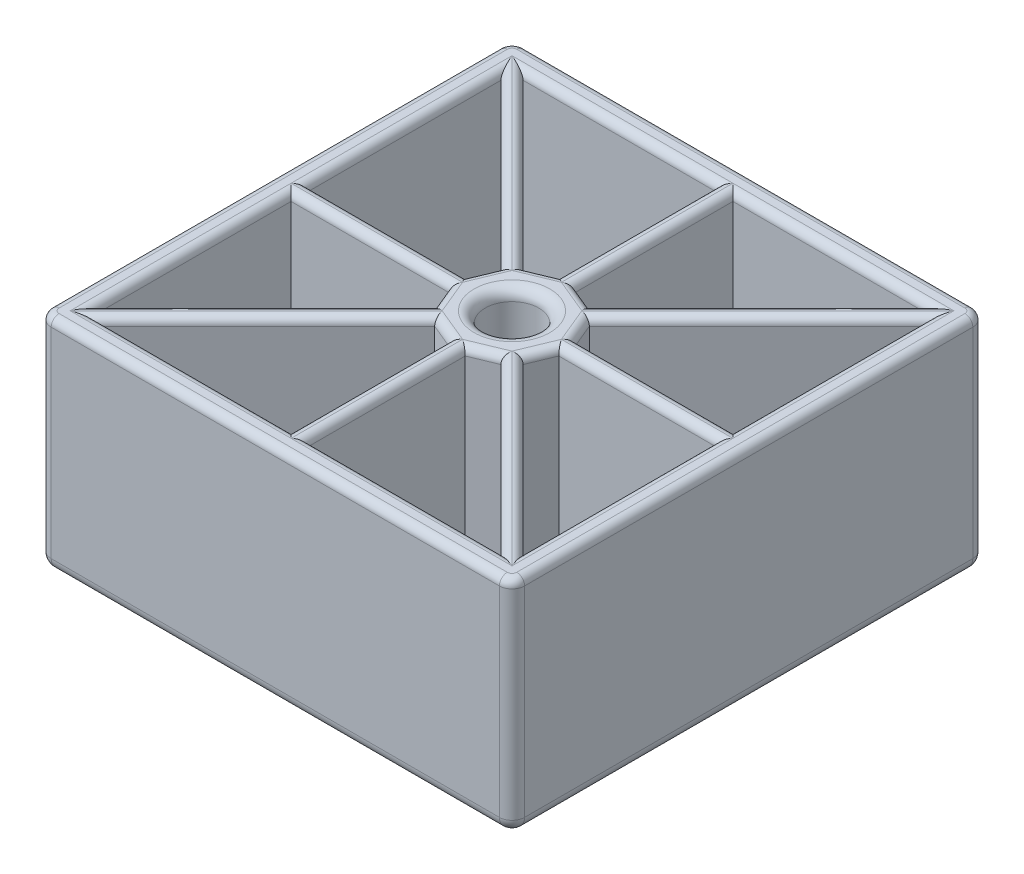
SolidWorks part; units mm, degrees
ref_plane "Front Plane" through (0, 0, 0) normal (0, 0, 1) x (1, 0, 0)
ref_plane "Top Plane" through (0, 0, 0) normal (0, 1, 0) x (1, 0, 0)
ref_plane "Right Plane" through (0, 0, 0) normal (1, 0, 0) x (0, 0, -1)
sketch "Sketch1" plane through (0, 0, 0) normal (0, 1, 0) x (1, 0, 0)
  line L1 (15, -15) -> (-15, -15)
  line L2 (15, -15) -> (15, 15)
  line L3 (15, 15) -> (-15, 15)
  line L4 (-15, -15) -> (-15, 15)
  line L5 (15, -15) -> (-15, 15) construction
  line L6 (15, 15) -> (-15, -15) construction
  point P0 (0, 0)
  dimension "D1" = 30
extrude "Boss-Extrude1" add sketch "Sketch1" along normal blind 14 contours L2 L1 L4 L3
sketch "Sketch2" plane through (0, 14, 0) normal (0, 1, 0) x (1, 0, 0)
  circle A0 centre (0, 0) radius 1.7
extrude "Cut-Extrude1" cut sketch "Sketch2" against normal blind 12
sketch "Sketch3" plane through (0, 14, 0) normal (0, 1, 0) x (1, 0, 0)
  line L0 (-15, 15) -> (15, -15) construction
  line L1 (15, 15) -> (-15, -15) construction
  line L2 (-13.5, -0.5) -> (13.5, -0.5) construction
  line L3 (13.5, -13.5) -> (-13.5, -13.5) construction
  line L4 (13.5, -13.5) -> (13.5, 13.5) construction
  line L5 (13.5, 13.5) -> (-13.5, 13.5) construction
  line L6 (-13.5, -13.5) -> (-13.5, 13.5) construction
  line L7 (13.5, -13.5) -> (-13.5, 13.5) construction
  line L8 (13.5, 13.5) -> (-13.5, -13.5) construction
  line L9 (-13.5, -0.5) -> (-13.5, 0.5) construction
  line L10 (0.5, -13.5) -> (-0.5, -13.5) construction
  line L11 (0.5, -13.5) -> (0.5, 13.5) construction
  line L12 (0.5, 13.5) -> (-0.5, 13.5) construction
  line L13 (-0.5, -13.5) -> (-0.5, 13.5) construction
  line L14 (0.5, -13.5) -> (-0.5, 13.5) construction
  line L15 (0.5, 13.5) -> (-0.5, -13.5) construction
  line L16 (-13.5, 0.5) -> (13.5, 0.5) construction
  line L17 (13.5, -0.5) -> (13.5, 0.5) construction
  line L18 (-0.5, 13.5) -> (-0.5, -13.5) construction
  line L19 (-0.5, 13.5) -> (0.5, 13.5) construction
  line L20 (0.5, 13.5) -> (0.5, -13.5) construction
  line L21 (-0.5, -13.5) -> (0.5, -13.5) construction
  line L22 (13.5, 0.5) -> (-13.5, 0.5) construction
  line L23 (13.5, 0.5) -> (13.5, -0.5) construction
  line L24 (13.5, -0.5) -> (-13.5, -0.5) construction
  line L25 (-13.5, 0.5) -> (-13.5, -0.5) construction
  line L26 (9.8995, -9.1924) -> (-9.1924, 9.8995) construction
  line L27 (-9.1924, 9.8995) -> (-9.8995, 9.1924) construction
  line L28 (9.1924, -9.8995) -> (-9.8995, 9.1924) construction
  line L29 (9.8995, -9.1924) -> (9.1924, -9.8995) construction
  line L30 (-9.1924, -9.8995) -> (9.8995, 9.1924) construction
  line L31 (-9.1924, -9.8995) -> (-9.8995, -9.1924) construction
  line L32 (-9.8995, -9.1924) -> (9.1924, 9.8995) construction
  line L33 (9.8995, 9.1924) -> (9.1924, 9.8995) construction
  line L34 (2.0959, 2.803) -> (12.7929, 13.5)
  line L35 (12.7929, 13.5) -> (0.5, 13.5)
  line L36 (0.5, 13.5) -> (0.5, 3.4641)
  line L37 (2.803, 2.0959) -> (13.5, 12.7929)
  line L38 (13.5, 12.7929) -> (13.5, 0.5)
  line L39 (13.5, 0.5) -> (3.4641, 0.5)
  line L40 (3.4641, -0.5) -> (13.5, -0.5)
  line L41 (2.803, -2.0959) -> (13.5, -12.7929)
  line L42 (13.5, -12.7929) -> (13.5, -0.5)
  line L43 (2.0959, -2.803) -> (12.7929, -13.5)
  line L44 (12.7929, -13.5) -> (0.5, -13.5)
  line L45 (0.5, -13.5) -> (0.5, -3.4641)
  line L46 (-2.0959, -2.803) -> (-12.7929, -13.5)
  line L47 (-12.7929, -13.5) -> (-0.5, -13.5)
  line L48 (-0.5, -13.5) -> (-0.5, -3.4641)
  line L49 (-2.803, -2.0959) -> (-13.5, -12.7929)
  line L50 (-13.5, -12.7929) -> (-13.5, -0.5)
  line L51 (-13.5, -0.5) -> (-3.4641, -0.5)
  line L52 (-2.803, 2.0959) -> (-13.5, 12.7929)
  line L53 (-13.5, 12.7929) -> (-13.5, 0.5)
  line L54 (-13.5, 0.5) -> (-3.4641, 0.5)
  line L55 (-2.0959, 2.803) -> (-12.7929, 13.5)
  line L56 (-12.7929, 13.5) -> (-0.5, 13.5)
  line L57 (-0.5, 13.5) -> (-0.5, 3.4641)
  line L58 (2.0959, 2.803) -> (0.5, 3.4641)
  line L59 (-0.5, 3.4641) -> (-2.0959, 2.803)
  line L60 (-2.803, 2.0959) -> (-3.4641, 0.5)
  line L61 (-2.803, -2.0959) -> (-3.4641, -0.5)
  line L62 (-2.0959, -2.803) -> (-0.5, -3.4641)
  line L63 (0.5, -3.4641) -> (2.0959, -2.803)
  line L64 (2.803, -2.0959) -> (3.4641, -0.5)
  line L65 (3.4641, 0.5) -> (2.803, 2.0959)
  point P8 (0, 0)
  point P16 (0, 0)
  point P34 (0, 0)
  point P42 (0, 0)
  dimension "D1" = 1
  dimension "D2" = 4
  dimension "D3" = 2
extrude "Cut-Extrude2" cut sketch "Sketch3" against normal blind 11
fillet "Fillet1" radius 0.7 1 edges at (0, 14, 1.7)
fillet "Fillet2" radius 0.5 36 edges at (15, 14, 0) (0, 14, 15) (-15, 14, 0) (0, 14, -15) (-7.4444, 14, -8.1515) (-1.298, 14, -3.1336) (-0.5, 14, -8.4821) (-6.6464, 14, -13.5) (3.1336, 14, 1.298) (8.1515, 14, 7.4444) (13.5, 14, 6.6464) (8.4821, 14, 0.5) (-8.1515, 14, -7.4444) (-13.5, 14, -6.6464) (-8.4821, 14, -0.5) (-3.1336, 14, -1.298) (-8.1515, 14, 7.4444) (-3.1336, 14, 1.298) (-8.4821, 14, 0.5) (-13.5, 14, 6.6464) (7.4444, 14, 8.1515) (1.298, 14, 3.1336) (0.5, 14, 8.4821) (6.6464, 14, 13.5) (7.4444, 14, -8.1515) (6.6464, 14, -13.5) (0.5, 14, -8.4821) (1.298, 14, -3.1336) (-7.4444, 14, 8.1515) (-6.6464, 14, 13.5) (-0.5, 14, 8.4821) (-1.298, 14, 3.1336) (8.1515, 14, -7.4444) (3.1336, 14, -1.298) (8.4821, 14, -0.5) (13.5, 14, -6.6464)
fillet "Fillet3" radius 0.8 4 edges at (-15, 0, 0) (0, 0, 15) (15, 0, 0) (0, 0, -15)
fillet "Fillet4" radius 0.8 12 edges at (-14.8536, 13.8536, -14.8536) (-14.8536, 13.8536, 14.8536) (14.8536, 13.8536, -14.8536) (14.8536, 13.8536, 14.8536) (14.7657, 0.2343, 14.7657) (14.7657, 0.2343, -14.7657) (-14.7657, 0.2343, 14.7657) (-14.7657, 0.2343, -14.7657) (15, 7.15, 15) (15, 7.15, -15) (-15, 7.15, 15) (-15, 7.15, -15)
